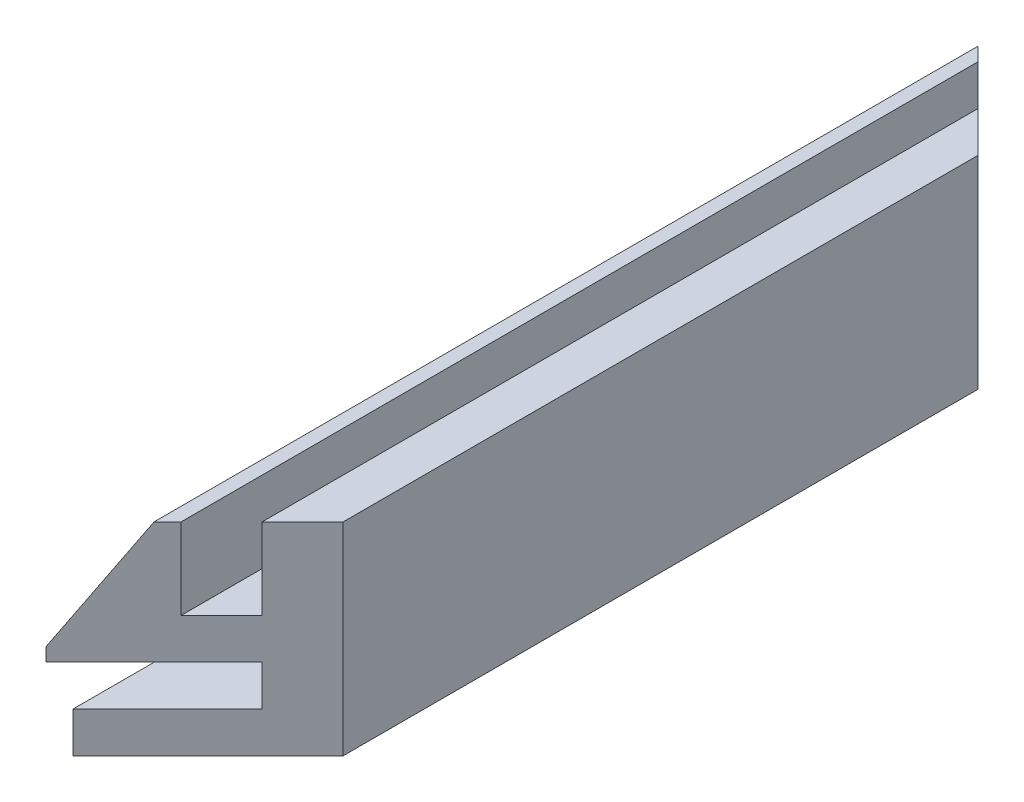
SolidWorks part; units mm, degrees
material "ABS"
ref_plane "Płaszczyzna przednia" through (0, 0, 0) normal (0, 0, 1) x (1, 0, 0)
ref_plane "Płaszczyzna górna" through (0, 0, 0) normal (0, 1, 0) x (1, 0, 0)
ref_plane "Płaszczyzna prawa" through (0, 0, 0) normal (1, 0, 0) x (0, 0, -1)
sketch "Szkic1" plane through (0, 0, 0) normal (0, 0, 1) x (1, 0, 0)
  line L0 (0, 0) -> (-7, 0)
  line L1 (-7, 0) -> (-7, -3)
  line L2 (-7, -3) -> (-0.5068, -3)
  line L3 (0, 0) -> (0, 3)
  line L4 (0, 3) -> (-8, 3)
  line L5 (-8, 3) -> (-8, 4)
  line L6 (-0.5068, -3) -> (3, -3)
  line L7 (3, -3) -> (3, 12)
  line L8 (3, 12) -> (0, 12)
  line L9 (0, 12) -> (0, 6)
  line L10 (0, 6) -> (-3, 6)
  line L11 (-3, 6) -> (-3, 12)
  line L12 (-3, 12) -> (-4, 12)
  line L13 (-4, 12) -> (-8, 4)
  point P15 (-7, 3)
  point P16 (-7.762, 3)
  point P17 (0, 0)
  dimension "D1" = 3
  dimension "D2" = 3
  dimension "D3" = 1
  dimension "D4" = 3
  dimension "D5" = 3
  dimension "D6" = 1
  dimension "D7" = 7
  dimension "D8" = 8
  dimension "D9" = 15
  dimension "D10" = 3
extrude "Dodanie-wyciągnięcie1" add sketch "Szkic1" along normal blind 70
sketch "Szkic2" plane through (0, 12, 0) normal (0, 1, 0) x (1, 0, 0)
  line L0 (3, -12) -> (-8, -1)
  line L1 (3, -70) -> (3, 0) construction
  line L2 (3, -59) -> (-8, -70)
  line L3 (-4, 0) -> (-8, 0) construction
  line L4 (-4, -70) -> (-8, -70) construction
  line L5 (3, 0) -> (0, 0) construction
  line L6 (0, 0) -> (-3, 0) construction
  line L7 (-3, 0) -> (-4, 0) construction
  line L8 (-8, -70) -> (-8, 0) construction
  line L9 (3, -70) -> (0, -70) construction
  line L10 (0, -70) -> (-3, -70) construction
  line L11 (-3, -70) -> (-4, -70) construction
  line L12 (3, 0) -> (0, 0)
  line L13 (0, 0) -> (-3, 0)
  line L14 (-3, 0) -> (-4, 0)
  line L15 (-4, 0) -> (-8, 0)
  line L16 (-8, -1) -> (-8, 0)
  line L17 (3, -70) -> (3, -59)
  line L18 (3, -70) -> (0, -70)
  line L19 (0, -70) -> (-3, -70)
  line L20 (-3, -70) -> (-4, -70)
  line L21 (-4, -70) -> (-8, -70)
  line L22 (3, -12) -> (3, 0)
  dimension "D1" = 45
  dimension "D2" = 45
  dimension "D3" = 47
extrude "Wytnij-wyciągnięcie1" cut sketch "Szkic2" against normal blind 47
